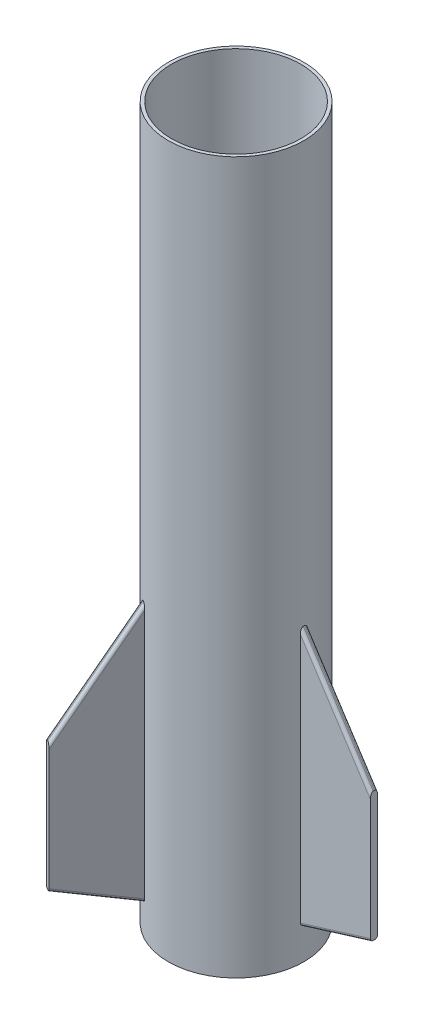
SolidWorks part; units mm, degrees
ref_plane "Front Plane" through (0, 0, 0) normal (0, 0, 1) x (1, 0, 0)
ref_plane "Top Plane" through (0, 0, 0) normal (0, 1, 0) x (1, 0, 0)
ref_plane "Right Plane" through (0, 0, 0) normal (1, 0, 0) x (0, 0, -1)
sketch "Sketch3" plane through (0, 0, 0) normal (0, 1, 0) x (1, 0, 0)
  circle A0 centre (0, 0) radius 40.005
  circle A1 centre (0, 0) radius 38.1
  dimension "D1" = 80.01
  dimension "D2" = 76.2
extrude "Boss-Extrude1" add sketch "Sketch3" along normal blind 419.1
sketch "Sketch4" plane through (0, 0, 0) normal (0, 0, 1) x (1, 0, 0)
  line L0 (40.005, 19.05) -> (40.005, 171.45)
  line L1 (40.005, 0) -> (40.005, 419.1) construction
  line L2 (40.005, 171.45) -> (81.28, 107.95)
  line L3 (81.28, 107.95) -> (81.28, 31.75)
  line L4 (81.28, 31.75) -> (40.005, 19.05)
  dimension "D1" = 76.2
  dimension "D2" = 152.4
  dimension "D3" = 41.275
  dimension "D4" = 12.7
  dimension "D5" = 19.05
extrude "Boss-Extrude2" add sketch "Sketch4" along normal blind 2.159 and the other way blind 2.159 separate body
fillet "Fillet1" radius 1.778 4 edges at (60.6425, 25.4, 2.159) (60.6425, 25.4, -2.159) (60.6425, 139.7, 2.159) (60.6425, 139.7, -2.159)
sketch "Sketch5" plane through (0, 0, 0) normal (0, 0, 1) x (1, 0, 0)
  line L0 (0, 0) -> (0, 465.0168) construction
pattern_circular "CirPattern1" count 3 over 360 about axis through (0, 0, 0) along (0, 1, 0) reverse direction yes of bodies 102
